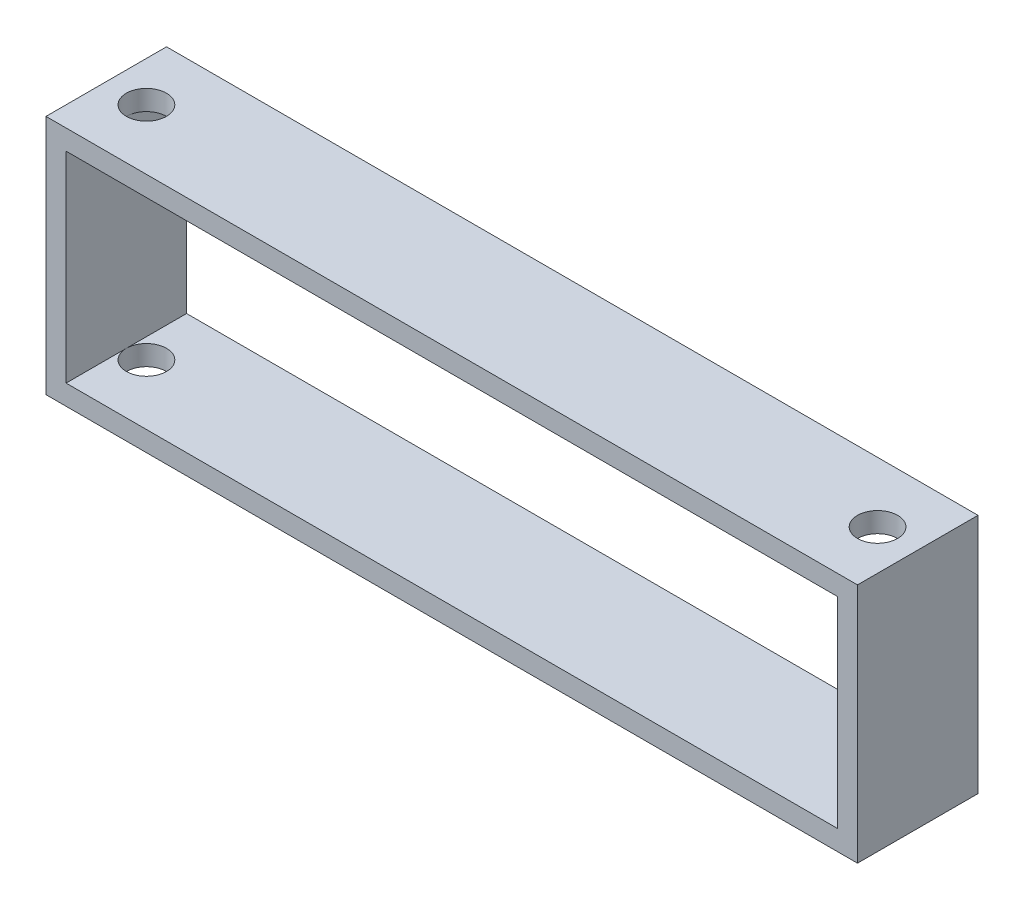
SolidWorks part; units mm, degrees
ref_plane "Alzado" through (0, 0, 0) normal (0, 0, 1) x (1, 0, 0)
ref_plane "Planta" through (0, 0, 0) normal (0, 1, 0) x (1, 0, 0)
ref_plane "Vista lateral" through (0, 0, 0) normal (1, 0, 0) x (0, 0, -1)
sketch "Croquis1" plane through (0, 0, 0) normal (0, 1, 0) x (1, 0, 0)
  line L1 (-47.0621, -10.9016) -> (154.9379, -10.9016)
  line L2 (-47.0621, -10.9016) -> (-47.0621, 19.0984)
  line L3 (-47.0621, 19.0984) -> (154.9379, 19.0984)
  line L4 (154.9379, -10.9016) -> (154.9379, 19.0984)
  circle A0 centre (-37.0621, 4.0984) radius 5
  circle A1 centre (144.9379, 4.0984) radius 5
  dimension "D3" = 10
  dimension "D4" = 10
  dimension "D1" = 30
  dimension "D2" = 202
  dimension "D5" = 10
  dimension "D6" = 15
  dimension "D7" = 182
  dimension "D8" = 15
extrude "Saliente-Extruir1" add sketch "Croquis1" along normal blind 60
sketch "Croquis2" plane through (0, 0, 10.9016) normal (0, 0, 1) x (1, 0, 0)
  line L0 (-47.0621, 60) -> (-47.0621, 0) construction
  line L1 (-42.0621, 55) -> (149.9379, 55)
  line L2 (-42.0621, 55) -> (-42.0621, 5)
  line L3 (-42.0621, 5) -> (149.9379, 5)
  line L4 (149.9379, 55) -> (149.9379, 5)
  line L5 (-47.0621, 0) -> (154.9379, 0) construction
  dimension "D1" = 50
  dimension "D2" = 192
  dimension "D3" = 5
  dimension "D4" = 5
extrude "Cortar-Extruir1" cut sketch "Croquis2" against normal through all
ref_axis "z1" through (-37.0621, 114.2761, -4.0984) along (0, -1, 0)
ref_axis "z2" through (144.9379, 101.8378, -4.0984) along (0, -1, 0)
